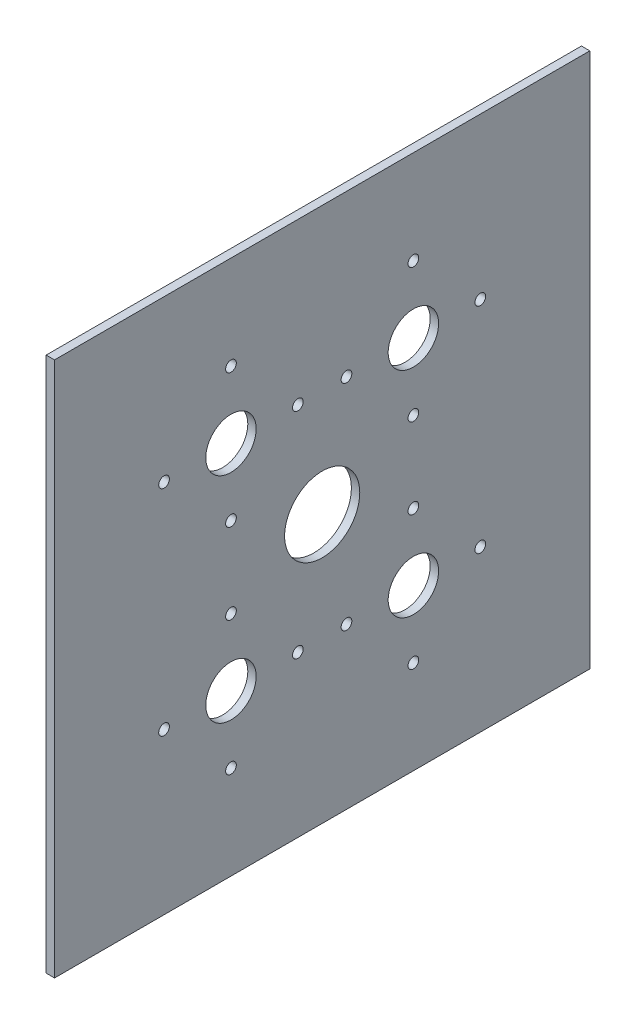
SolidWorks part; units mm, degrees
ref_plane "Front" through (0, 0, 0) normal (0, 0, 1) x (1, 0, 0)
ref_plane "Top" through (0, 0, 0) normal (0, 1, 0) x (1, 0, 0)
ref_plane "Right" through (0, 0, 0) normal (1, 0, 0) x (0, 0, -1)
sketch "Sketch1" plane through (0, 0, 0) normal (1, 0, 0) x (0, 0, -1)
  line L1 (101.6, 101.6) -> (-101.6, 101.6)
  line L2 (101.6, 101.6) -> (101.6, -101.6)
  line L3 (101.6, -101.6) -> (-101.6, -101.6)
  line L4 (-101.6, 101.6) -> (-101.6, -101.6)
  line L5 (101.6, 101.6) -> (-101.6, -101.6) construction
  line L6 (101.6, -101.6) -> (-101.6, 101.6) construction
  point P0 (0, 0)
  dimension "D1" = 203.2
  dimension "D2" = 203.2
base flange "Base-Flange1" sketch "Sketch1" thickness 3.175 reverse thickness direction no parameters "D1"=1
sketch "Sketch6" plane through (0, 0, 0) normal (1, 0, 0) x (0, 0, -1)
  line L0 (101.6, 101.6) -> (-101.6, 101.6) construction
  line L1 (0, 101.6) -> (0, -101.6) construction
  line L2 (-101.6, -101.6) -> (101.6, -101.6) construction
  line L3 (-101.6, 0) -> (101.6, 0) construction
  line L4 (-101.6, 101.6) -> (-101.6, -101.6) construction
  line L5 (101.6, -101.6) -> (101.6, 101.6) construction
  circle A0 centre (-34.6219, 40.677) radius 9.5631
  circle A1 centre (34.6219, 40.677) radius 9.5631
  circle A2 centre (-34.6219, -40.677) radius 9.5631
  circle A3 centre (34.6219, -40.677) radius 9.5631
  circle A4 centre (0, 0) radius 14.2621
  circle A5 centre (-34.6219, 66.077) radius 2.032
  circle A6 centre (-34.6219, 15.277) radius 2.032
  circle A7 centre (-60.0219, 40.677) radius 2.032
  circle A8 centre (-9.2219, 40.677) radius 2.032
  circle A9 centre (34.6219, 15.277) radius 2.032
  circle A10 centre (60.0219, 40.677) radius 2.032
  circle A11 centre (9.2219, 40.677) radius 2.032
  circle A12 centre (34.6219, 66.077) radius 2.032
  circle A13 centre (34.6219, -15.277) radius 2.032
  circle A14 centre (60.0219, -40.677) radius 2.032
  circle A15 centre (34.6219, -66.077) radius 2.032
  circle A16 centre (9.2219, -40.677) radius 2.032
  circle A17 centre (-9.2219, -40.677) radius 2.032
  circle A18 centre (-34.6219, -15.277) radius 2.032
  circle A19 centre (-60.0219, -40.677) radius 2.032
  circle A20 centre (-34.6219, -66.077) radius 2.032
  dimension "D1" = 53.4162
  dimension "D8" = 19.1262
  dimension "D9" = 19.1262
  dimension "D10" = 19.1262
  dimension "D11" = 19.1262
  dimension "D12" = 28.5242
  dimension "D14" = 0
  dimension "D19" = 4.064
  dimension "D20" = 4.064
  dimension "D21" = 4.064
  dimension "D22" = 4.064
  dimension "D23" = 50.8
  dimension "D2" = 53.4162
  dimension "D3" = 53.4162
  dimension "D4" = 53.4162
  dimension "D5" = 0
  dimension "D6" = 0
  dimension "D7" = 0
  dimension "D13" = 69.2437
  dimension "D15" = 25.4
  dimension "D16" = 25.4
  dimension "D17" = 25.4
  dimension "D18" = 25.4
  dimension "D24" = 35.921
  dimension "D25" = 25.4
extrude "Cut-Extrude1" cut sketch "Sketch6" against normal blind 3.175 normal cut yes
sketch "Bend-Lines1" [suppressed] plane through (0, 0, 0) normal (0, 1, 0) x (1, 0, 0)
sketch "Bounding-Box1" [suppressed] plane through (0, 0, 0) normal (0, 1, 0) x (1, 0, 0)
sheet metal parameters "Sheet-Metal1" thickness 3.175 parameters "D1"=1
flat pattern "Flat-Pattern1" [suppressed]
sketch "Bend-Lines2" plane through (0, 0, 0) normal (0, 1, 0) x (1, 0, 0)
sketch3d "Bounding-Box2" [suppressed]
  line L0 (-101.6, -101.6, 0) -> (101.6, -101.6, 0) construction
  line L1 (-101.6, 101.6, 0) -> (101.6, 101.6, 0) construction
  line L2 (-101.6, -101.6, 0) -> (-101.6, 101.6, 0) construction
  line L3 (101.6, -101.6, 0) -> (101.6, 101.6, 0) construction
sheet metal parameters "Sheet-Metal2" thickness 3.175 parameters "D1"=1
flat pattern "Flat-Pattern1"
sketch "Bend-Lines2" plane through (0, 0, 0) normal (0, 1, 0) x (1, 0, 0)
sketch3d "Bounding-Box2" [suppressed]
  line L0 (101.6, -101.6, 0) -> (-101.6, -101.6, 0) construction
  line L1 (101.6, 101.6, 0) -> (-101.6, 101.6, 0) construction
  line L2 (101.6, -101.6, 0) -> (101.6, 101.6, 0) construction
  line L3 (-101.6, -101.6, 0) -> (-101.6, 101.6, 0) construction
